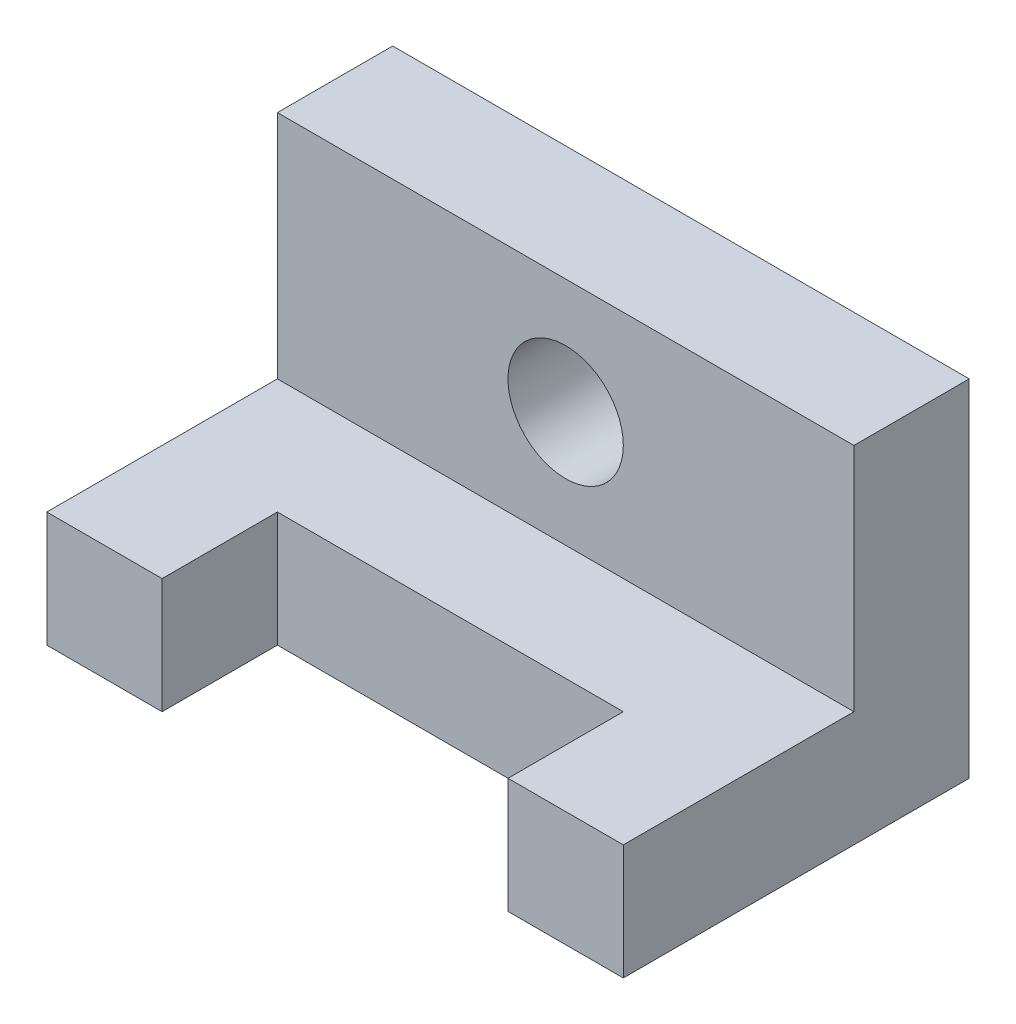
SolidWorks part; units mm, degrees
ref_plane "Front Plane" through (0, 0, 0) normal (0, 0, 1) x (1, 0, 0)
ref_plane "Top Plane" through (0, 0, 0) normal (0, 1, 0) x (1, 0, 0)
ref_plane "Right Plane" through (0, 0, 0) normal (1, 0, 0) x (0, 0, -1)
sketch "Sketch1" plane through (0, 0, 0) normal (0, 1, 0) x (1, 0, 0)
  line L1 (0, 0) -> (100, 0)
  line L2 (0, 0) -> (0, 60)
  line L3 (0, 60) -> (100, 60)
  line L4 (100, 0) -> (100, 60)
  line L5 (0, 60) -> (100, 60)
  line L6 (0, 60) -> (0, 40)
  line L7 (0, 40) -> (100, 40)
  line L8 (100, 60) -> (100, 40)
  line L9 (20, 0) -> (80, 0)
  line L10 (20, 0) -> (20, 20)
  line L11 (20, 20) -> (80, 20)
  line L12 (80, 0) -> (80, 20)
  dimension "D1" = 100
  dimension "D2" = 60
  dimension "D3" = 20
  dimension "D4" = 20
  dimension "D5" = 20
  dimension "D6" = 20
extrude "Boss-Extrude1" add sketch "Sketch1" along normal blind 20 contours L12 L1 L4 L7 L2 L10 L11 region at (50, 0, -24.2857)
extrude "Boss-Extrude2" add sketch "Sketch1<3>" along normal blind 60 contours L2 L7 L4 L3 region at (50, 0, -50)
sketch "Sketch1<3>" plane through (0, 0, 0) normal (0, 1, 0) x (1, 0, 0) same geometry as "Sketch1"
sketch "Sketch2" plane through (0, 0, -40) normal (0, 0, 1) x (1, 0, 0)
  circle A0 centre (50, 40) radius 10
  dimension "D3" = 20
  dimension "D1" = 50
  dimension "D2" = 20
extrude "Cut-Extrude1" cut sketch "Sketch2" against normal through all
